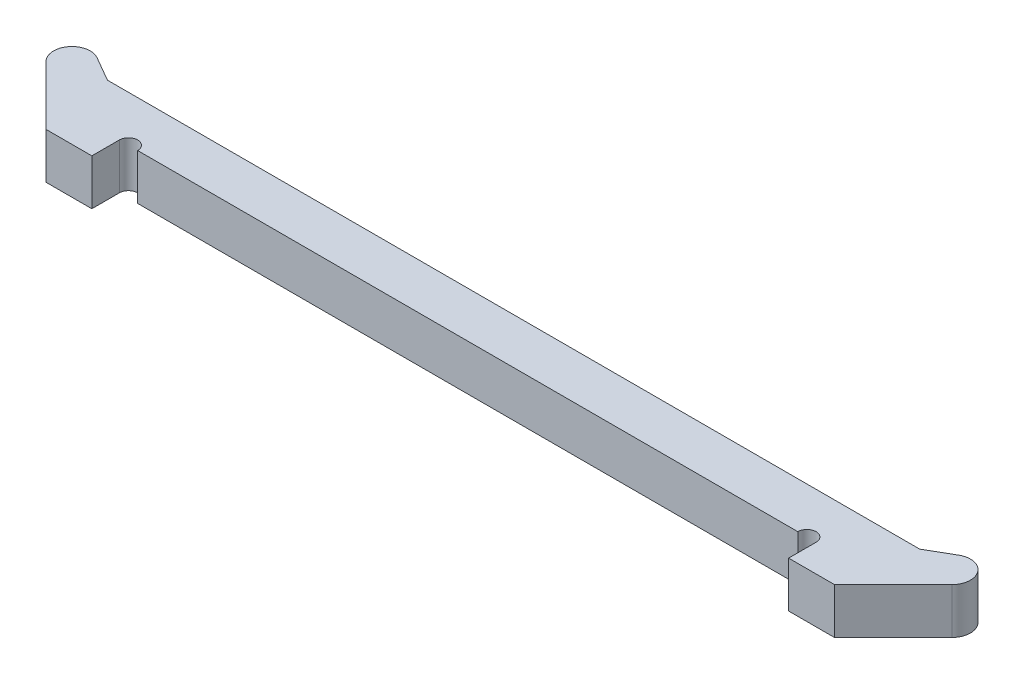
SolidWorks part; units mm, degrees
material "A2017"
ref_plane "正面" through (0, 0, 0) normal (0, 0, 1) x (1, 0, 0)
ref_plane "平面" through (0, 0, 0) normal (0, 1, 0) x (1, 0, 0)
ref_plane "右側面" through (0, 0, 0) normal (1, 0, 0) x (0, 0, -1)
sketch "ｽｹｯﾁ1" plane through (0, 0, 0) normal (0, 1, 0) x (1, 0, 0)
  line L0 (0, 0) -> (0, 22.3684) construction
  line L1 (-38, 0) -> (38, 0)
  line L2 (38, 0) -> (38, -3)
  line L3 (38, -3) -> (43, -3)
  line L4 (-38, -3) -> (-43, -3)
  line L5 (-38, 0) -> (-38, -3)
  line L6 (43, -3) -> (49.4142, 3.4142)
  line L7 (-43, -3) -> (-49.4142, 3.4142)
  line L8 (-44.2972, 5) -> (44.2972, 5)
  line L9 (47, 6.5605) -> (44.2972, 5)
  line L10 (50, 8.3293) -> (50, -3) construction
  line L11 (-50, 8.3293) -> (-50, -3) construction
  line L12 (-47, 6.5605) -> (-44.2972, 5)
  line L13 (-43, -3) -> (-49.4142, 3.4142)
  arc A0 (49.4142, 3.4142) -> (47, 6.5605) centre (48, 4.8284) ccw
  arc A1 (-49.4142, 3.4142) -> (-47, 6.5605) centre (-48, 4.8284) cw
  point P14 (0, 5)
  dimension "D8" = 2
  dimension "D1" = 5
  dimension "D2" = 3
  dimension "D3" = 76
  dimension "D4" = 45
  dimension "D5" = 30
  dimension "D6" = 5
  dimension "D7" = 100
extrude "ﾎﾞｽ - 押し出し1" add sketch "ｽｹｯﾁ1" along normal mid plane 5 contours A1 L7 L4 L5 L1 L2 L3 L6 A0 L9 L8 L12 region at (0, 0, -2.3316)
sketch "ｽｹｯﾁ2" plane through (0, 2.5, 0) normal (0, 1, 0) x (1, 0, 0)
  line L0 (-38, 0) -> (38, 0) construction
  circle A0 centre (-37, 0) radius 1
  circle A1 centre (37, 0) radius 1
  dimension "D1" = 2
extrude "ｶｯﾄ - 押し出し1" cut sketch "ｽｹｯﾁ2" against normal up to surface (5 mm away) up to face at (0, -2.5, -1.6722)
